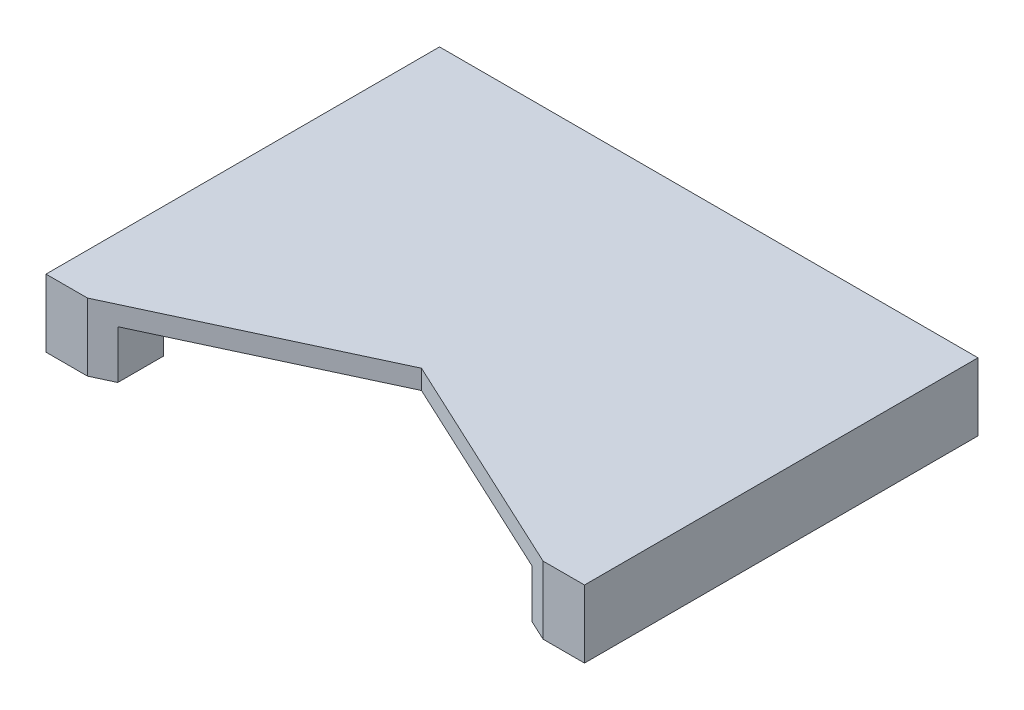
SolidWorks part; units mm, degrees
ref_plane "Front Plane" through (0, 0, 0) normal (0, 0, 1) x (1, 0, 0)
ref_plane "Top Plane" through (0, 0, 0) normal (0, 1, 0) x (1, 0, 0)
ref_plane "Right Plane" through (0, 0, 0) normal (1, 0, 0) x (0, 0, -1)
sketch "Sketch1" plane through (0, 0, 0) normal (0, 1, 0) x (1, 0, 0)
  line L1 (0, 0) -> (78, 0)
  line L2 (0, 0) -> (0, 57)
  line L3 (0, 57) -> (78, 57)
  line L4 (78, 0) -> (78, 57)
  dimension "D1" = 57
  dimension "D2" = 78
extrude "Boss-Extrude1" add sketch "Sketch1" along normal blind 9.8
sketch "Sketch2" plane through (0, 0, 0) normal (0, -1, 0) x (1, 0, 0)
  line L0 (78, -57) -> (0, -57) construction
  line L1 (6, -57) -> (72, -57)
  line L2 (6, -57) -> (6, -8)
  line L3 (6, -8) -> (72, -8)
  line L4 (72, -57) -> (72, -8)
  line L5 (0, -57) -> (0, 0) construction
  line L6 (78, 0) -> (78, -57) construction
  dimension "D1" = 6
  dimension "D2" = 6
  dimension "D3" = 49
extrude "Cut-Extrude1" cut sketch "Sketch2" against normal blind 7
sketch "Sketch3" plane through (0, 0, 0) normal (0, -1, 0) x (1, 0, 0)
  line L0 (72, -8) -> (6, -8) construction
  line L1 (9, -8) -> (69, -8)
  line L2 (9, -8) -> (9, 0)
  line L3 (9, 0) -> (69, 0)
  line L4 (69, -8) -> (69, 0)
  line L5 (0, 0) -> (78, 0) construction
  line L6 (0, -57) -> (0, 0) construction
  line L7 (78, 0) -> (78, -57) construction
  dimension "D1" = 9
  dimension "D2" = 9
extrude "Cut-Extrude2" cut sketch "Sketch3" against normal up to surface (7 mm away) up to face at (39, 7, -32.5)
sketch "Sketch4" plane through (0, 9.8, 0) normal (0, 1, 0) x (1, 0, 0)
  line L0 (0, 0) -> (78, 0) construction
  line L1 (6, 0) -> (39, 15.3882)
  line L2 (39, 15.3882) -> (72, 0)
  line L3 (39, 15.3882) -> (39, 57) construction
  line L4 (72, 0) -> (6, 0)
  line L5 (78, 57) -> (0, 57) construction
  dimension "D1" = 130
  dimension "D2" = 6
extrude "Cut-Extrude3" cut sketch "Sketch4" against normal up to next
